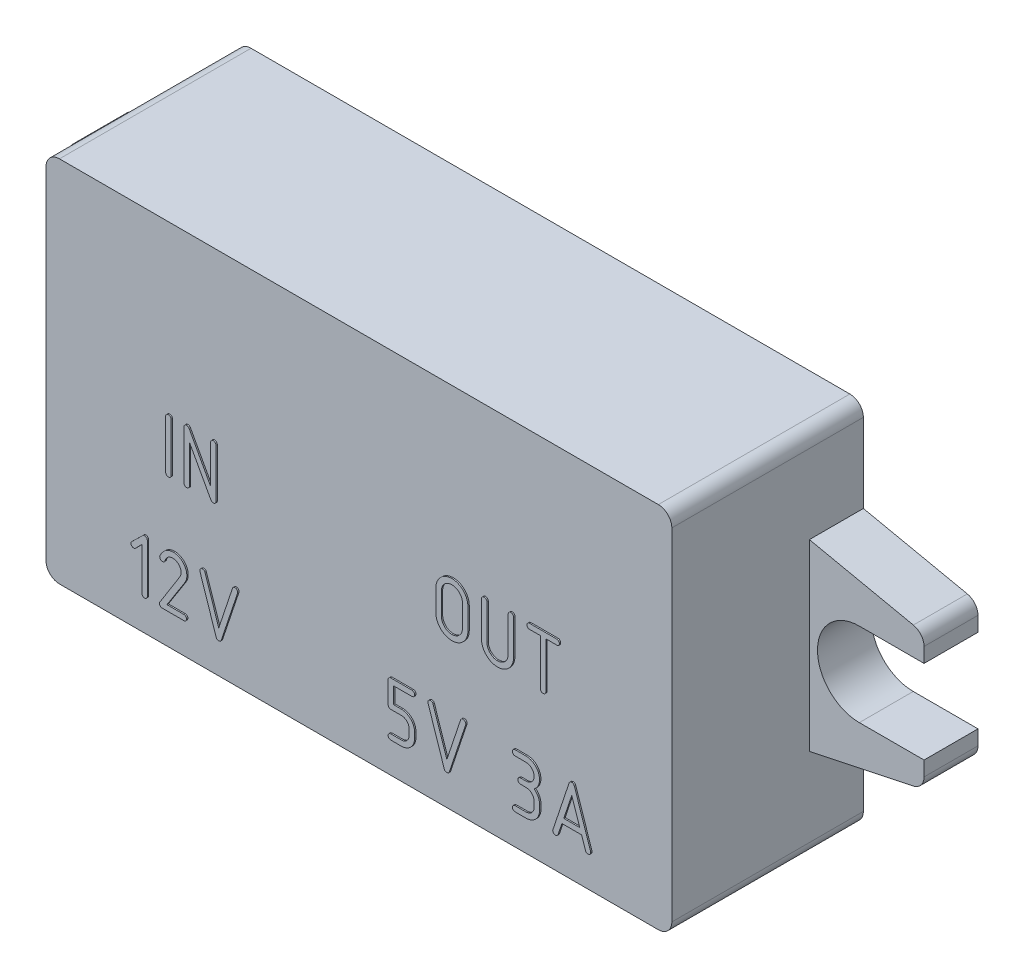
SolidWorks part; units mm, degrees
material "ABS"
ref_plane "Front Plane" through (0, 0, 0) normal (0, 0, 1) x (1, 0, 0)
ref_plane "Top Plane" through (0, 0, 0) normal (0, 1, 0) x (1, 0, 0)
ref_plane "Right Plane" through (0, 0, 0) normal (1, 0, 0) x (0, 0, -1)
sketch "Sketch1" plane through (0, 0, 0) normal (0, 0, 1) x (1, 0, 0)
  line L1 (-23.2, -13.65) -> (23.2, -13.65)
  line L2 (-23.2, -13.65) -> (-23.2, 13.65)
  line L3 (-23.2, 13.65) -> (23.2, 13.65)
  line L4 (23.2, -13.65) -> (23.2, 13.65)
  line L5 (-23.2, -13.65) -> (23.2, 13.65) construction
  line L6 (-23.2, 13.65) -> (23.2, -13.65) construction
  point P0 (0, 0)
  dimension "D1" = 27.3
  dimension "D2" = 46.4
extrude "boss_body" add sketch "Sketch1" along normal blind 14.2
sketch "Sketch2" plane through (0, 0, 0) normal (0, 0, 1) x (1, 0, 0)
  line L0 (-23.2, 6.8) -> (-31.7, 5)
  line L1 (-23.2, 13.65) -> (-23.2, -13.65) construction
  line L2 (-31.7, 5) -> (-31.7, -5)
  line L3 (-31.7, -5) -> (-23.2, -6.8)
  line L4 (-23.2, -6.8) -> (-23.2, 6.8)
  line L5 (0, 0) -> (0, 18.1999) construction
  line L6 (-31.7, 0) -> (-23.2, 0) construction
  dimension "D1" = 63.4
  dimension "D2" = 13.6
  dimension "D3" = 10
extrude "boss_arm" add sketch "Sketch2" along normal blind 4
sketch "Sketch3" plane through (0, 0, 4) normal (0, 0, 1) x (1, 0, 0)
  line L0 (-26.9, 3.1) -> (-31.7, 3.1)
  line L1 (-31.7, 5) -> (-31.7, -5) construction
  line L2 (-31.7, 3.1) -> (-31.7, -3.1)
  line L3 (-31.7, -3.1) -> (-26.9, -3.1)
  line L4 (-23.2, -6.8) -> (-23.2, 6.8) construction
  arc A0 (-26.9, -3.1) -> (-26.9, 3.1) centre (-26.9, 0) ccw
  point P10 (-23.8, 0)
  dimension "D1" = 3.1
  dimension "D2" = 0.6
extrude "cut_arm_notch" cut sketch "Sketch3" against normal through all
fillet "fillet_fingers" radius 1 2 edges at (-31.7, -5, 2) (-31.7, 5, 2)
mirror "Mirror1" about plane through (0, 0, 0) normal (1, 0, 0) of "fillet_fingers", "boss_arm", "cut_arm_notch"
sketch "Sketch4" plane through (0, 0, 14.2) normal (0, 0, 1) x (1, 0, 0)
  line L0 (-17.2, -2.65) -> (-17.2, -13.65) construction
  line L1 (-23.2, -13.65) -> (23.2, -13.65) construction
  line L2 (-17.2, -2.65) -> (-23.2, -2.65) construction
  line L3 (-23.2, 13.65) -> (-23.2, -13.65) construction
  text T0 " IN      OUT\r\n12V    5V 3A"
  dimension "D1" = 6
  dimension "D2" = 11
extrude "Boss-Extrude3" add sketch "Sketch4" along normal blind 0.1
sketch "sketch_screw_location" plane through (0, 0, 0) normal (0, 0, 1) x (1, 0, 0)
  circle A0 centre (-29.2, 0) radius 3.1
  circle A1 centre (29.2, 0) radius 3.1
  arc A2 (-26.9, -3.1) -> (-26.9, 3.1) centre (-26.9, 0) ccw construction
  point P4 (26.9, 0)
  point P5 (-26.9, 0)
  dimension "D1" = 2.3
  dimension "D2" = 2.3
ref_axis "left" through (-29.2, 0, 0) along (0, 0, -1)
ref_axis "right" through (29.2, 0, 0) along (0, 0, -1)
fillet "Fillet2" radius 1 4 edges at (23.2, -13.65, 7.1) (-23.2, -13.65, 7.1) (23.2, 13.65, 7.1) (-23.2, 13.65, 7.1)
ref_plane "fastener" through (30, 0, 0) normal (1, 0, 0) x (0, 0, -1)
equation "\"offset_screw\"= 2.3"
equation "\"D2@sketch_screw_location\" = \"offset_screw\""
equation "\"D1@sketch_screw_location\" = \"offset_screw\""
